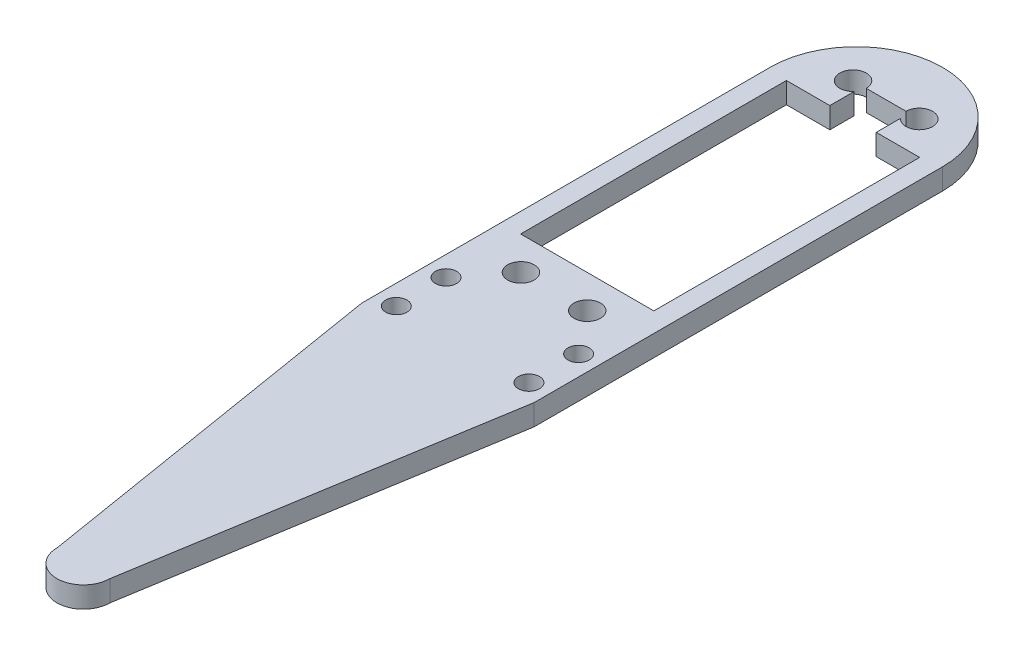
SolidWorks part; units mm, degrees
ref_plane "Front Plane" through (0, 0, 0) normal (0, 0, 1) x (1, 0, 0)
ref_plane "Top Plane" through (0, 0, 0) normal (0, 1, 0) x (1, 0, 0)
ref_plane "Right Plane" through (0, 0, 0) normal (1, 0, 0) x (0, 0, -1)
sketch "Sketch2" plane through (0, 0, 0) normal (0, 1, 0) x (1, 0, 0)
  line L0 (-13, 0) -> (-13, -61.6)
  line L1 (13, 0) -> (13, -61.6)
  line L2 (-13, -61.6) -> (-4, -116.6)
  line L3 (13, -61.6) -> (4, -116.6)
  line L4 (0, 13) -> (0, -120.6) construction
  line L5 (-4, -116.6) -> (4, -116.6) construction
  line L6 (-10.05, -0.5) -> (10.05, -0.5)
  line L7 (-10.05, -0.5) -> (-10.05, -40.6)
  line L8 (-10.05, -40.6) -> (10.05, -40.6)
  line L9 (10.05, -0.5) -> (10.05, -40.6)
  line L10 (-10.05, -0.5) -> (10.05, -40.6) construction
  line L11 (-10.05, -40.6) -> (10.05, -0.5) construction
  arc A0 (13, 0) -> (-13, 0) centre (0, 0) ccw
  arc A1 (-4, -116.6) -> (4, -116.6) centre (0, -116.6) ccw
  circle A2 centre (-5, 4.5) radius 2
  circle A4 centre (-5, -45.6) radius 2
  circle A5 centre (5, -45.6) radius 2
  circle A6 centre (5, 4.5) radius 2
  point P15 (0, -20.55)
  dimension "D1" = 4
  dimension "D8" = 13
  dimension "D10" = 4
  dimension "D2" = 50.1
  dimension "D3" = 5
  dimension "D4" = 4.5
  dimension "D5" = 40.1
  dimension "D6" = 20.1
  dimension "D7" = 5
  dimension "D9" = 55
  dimension "D11" = 16
extrude "Boss-Extrude1" add sketch "Sketch2" along normal blind 3.175
sketch "Sketch3" plane through (0, 3.175, 0) normal (0, 1, 0) x (1, 0, 0)
  circle A0 centre (10, -59.4) radius 1.6 construction
  circle A1 centre (10, -51.9) radius 1.6 construction
  circle A2 centre (-10, -59.4) radius 1.6 construction
  circle A3 centre (-10, -51.9) radius 1.6 construction
  circle A4 centre (10, -59.4) radius 1.6
  circle A5 centre (10, -51.9) radius 1.6
  circle A6 centre (-10, -59.4) radius 1.6
  circle A7 centre (-10, -51.9) radius 1.6
extrude "Cut-Extrude1" cut sketch "Sketch3" against normal through all both and the other way through all
sketch "Sketch4" plane through (0, 3.175, 0) normal (0, 1, 0) x (1, 0, 0)
  line L0 (10.05, -0.5) -> (-10.05, -0.5) construction
  line L1 (-3.5, 4.5) -> (3.5, 4.5)
  line L2 (-3.5, 4.5) -> (-3.5, -0.5)
  line L3 (-3.5, -0.5) -> (3.5, -0.5)
  line L4 (3.5, 4.5) -> (3.5, -0.5)
  line L5 (-3.5, 4.5) -> (3.5, -0.5) construction
  line L6 (-3.5, -0.5) -> (3.5, 4.5) construction
  point P0 (0, 2)
  point P5 (0, -0.5)
  dimension "D1" = 7
  dimension "D2" = 5
extrude "Cut-Extrude2" cut sketch "Sketch4" along direction (0, 1, 0) on the side against the normal up to surface (3.175 mm away) up to face at (10, 0, 53.5)
